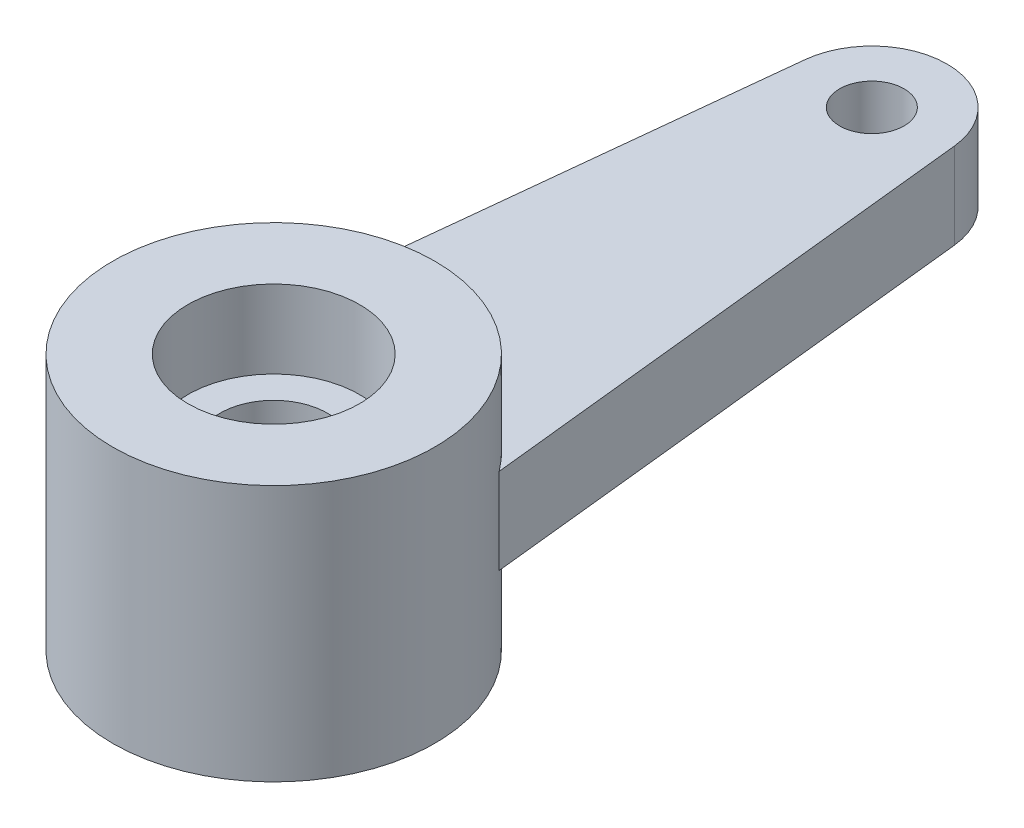
SolidWorks part; units mm, degrees
ref_plane "Front Plane" through (0, 0, 0) normal (0, 0, 1) x (1, 0, 0)
ref_plane "Top Plane" through (0, 0, 0) normal (0, 1, 0) x (1, 0, 0)
ref_plane "Right Plane" through (0, 0, 0) normal (1, 0, 0) x (0, 0, -1)
sketch "Sketch1" plane through (0, 0, 0) normal (0, 1, 0) x (1, 0, 0)
  line L0 (0, 0) -> (0, 22841.5203) construction
  line L1 (0, 0) -> (22841.5203, 0) construction
  circle A0 centre (0, 0) radius 7.5
  dimension "D1" = 15
extrude "Boss-Extrude1" add sketch "Sketch1" along normal mid plane 11.95
sketch "Sketch2" plane through (0, 5.975, 0) normal (0, 1, 0) x (1, 0, 0)
  circle A0 centre (0, 0) radius 2.5
  dimension "D1" = 5
extrude "Rod-Cutout" cut sketch "Sketch2" against normal through all and the other way through all
sketch "Sketch3" plane through (0, 5.975, 0) normal (0, 1, 0) x (1, 0, 0)
  circle A0 centre (0, 0) radius 4
  dimension "D1" = 8
extrude "Bearing-Cutout" cut sketch "Sketch3" against normal blind 3.63
mirror "Mirror1" about plane through (0, 0, 0) normal (0, 1, 0) of "Bearing-Cutout"
sketch "Sketch4" plane through (0, 0, 0) normal (0, 1, 0) x (1, 0, 0)
  line L0 (0, 0) -> (0, -50000) construction
  line L1 (0, 0) -> (-50000, 0) construction
  line L2 (-6, 0) -> (6, 0)
  line L3 (6, 0) -> (6, 4.5)
  line L4 (6, 4.5) -> (3.4804, 28.2197)
  line L5 (-6, 0) -> (-6, 4.5)
  line L6 (-6, 4.5) -> (-3.4804, 28.2197)
  circle A0 centre (0, 0) radius 7.5 construction
  arc A1 (3.4804, 28.2197) -> (-3.4804, 28.2197) centre (0, 27.85) ccw
  point P26 (0, 0)
  dimension "D1" = 7
  dimension "D2" = 12
  dimension "D3" = 27.85
extrude "SteeringLink-Mount" add sketch "Sketch4" along normal mid plane 4
sketch "Sketch5" plane through (0, 5.975, 0) normal (0, 1, 0) x (1, 0, 0)
  circle A0 centre (0, 0) radius 2.5
  circle A1 centre (0, 0) radius 2.5 construction
extrude "Cut-Extrude3" cut sketch "Sketch5" against normal through all
sketch "Sketch6" plane through (0, 2, 0) normal (0, 1, 0) x (1, 0, 0)
  line L0 (0, 0) -> (0, 50000) construction
  circle A0 centre (0, 27.85) radius 3.5 construction
  arc A1 (3.4804, 28.2197) -> (-3.4804, 28.2197) centre (0, 27.85) ccw construction
  circle A2 centre (0, 27.85) radius 1.5
  dimension "D1" = 3
extrude "LinkageMount-Hole" cut sketch "Sketch6" against normal blind 10
